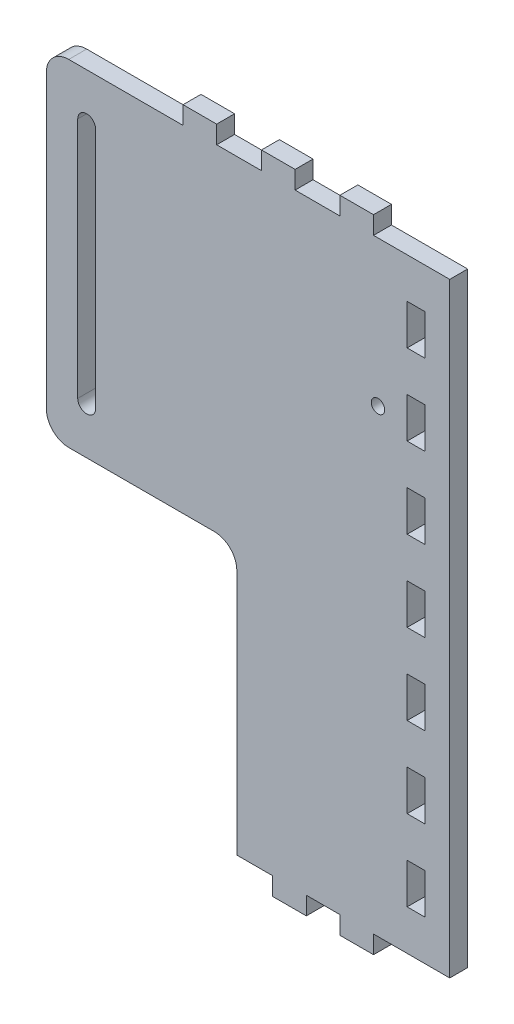
SolidWorks part; units mm, degrees
material "Beech"
ref_plane "Front" through (0, 0, 0) normal (0, 0, 1) x (1, 0, 0)
ref_plane "Top" through (0, 0, 0) normal (0, 1, 0) x (1, 0, 0)
ref_plane "Right" through (0, 0, 0) normal (1, 0, 0) x (0, 0, -1)
sketch "Sketch1" plane through (0, 0, 0) normal (0, 0, 1) x (1, 0, 0)
  line L0 (58, 135) -> (58, 70) construction
  line L1 (-90, -135) -> (90, -135) construction
  line L2 (-90, -135) -> (-90, 135) construction
  line L3 (-90, 135) -> (90, 135) construction
  line L4 (90, -135) -> (90, 135) construction
  line L5 (-90, -135) -> (90, 135) construction
  line L6 (-90, 135) -> (90, -135) construction
  line L7 (58, 70) -> (90, 70) construction
  line L8 (-90, -15) -> (90, -15) construction
  line L9 (-76, 135) -> (-76, -15) construction
  line L10 (-68, -15) -> (-68, 135) construction
  line L11 (-5, -15) -> (-5, -135) construction
  line L12 (90, 135) -> (-80, 135)
  line L13 (-90, 125) -> (-90, -5)
  line L14 (-80, -15) -> (-15, -15)
  line L15 (-5, -25) -> (-5, -135)
  line L16 (-5, -135) -> (90, -135)
  line L17 (90, -135) -> (90, 135)
  line L18 (-72, 114) -> (-72, 6) construction
  line L19 (-68, 114) -> (-68, 6)
  line L20 (-76, 114) -> (-76, 6)
  arc A0 (-68, 114) -> (-76, 114) centre (-72, 114) ccw
  arc A1 (-76, 6) -> (-68, 6) centre (-72, 6) ccw
  circle A2 centre (58, 70) radius 3
  arc A3 (-15, -15) -> (-5, -25) centre (-15, -25) cw
  arc A4 (-90, -5) -> (-80, -15) centre (-80, -5) ccw
  arc A5 (-80, 135) -> (-90, 125) centre (-80, 125) ccw
  point P0 (0, 0)
  point P19 (-72, 60)
  point P25 (-68, 60)
  point P26 (-76, 60)
  point P36 (0, 0)
  point P37 (0, 0)
  dimension "D10" = 6
  dimension "D11" = 10
  dimension "D1" = 180
  dimension "D2" = 120
  dimension "D3" = 270
  dimension "D4" = 95
  dimension "D5" = 14
  dimension "D6" = 8
  dimension "D7" = 65
  dimension "D8" = 32
  dimension "D9" = 108
extrude "Boss-Extrude1" add sketch "Sketch1" along normal blind 8
sketch "Sketch2" plane through (0, 0, 8) normal (0, 0, 1) x (1, 0, 0)
  line L0 (90, -135) -> (90, 135) construction
  line L1 (79, -117) -> (71, -117)
  line L2 (79, -117) -> (79, -99)
  line L3 (79, -99) -> (71, -99)
  line L4 (71, -117) -> (71, -99)
  line L5 (79, -117) -> (71, -99) construction
  line L6 (79, -99) -> (71, -117) construction
  line L7 (-5, -135) -> (90, -135) construction
  line L8 (79, -63) -> (71, -63)
  line L9 (71, -81) -> (71, -63)
  line L10 (79, -81) -> (71, -81)
  line L11 (79, -81) -> (79, -63)
  line L12 (79, -27) -> (71, -27)
  line L13 (71, -45) -> (71, -27)
  line L14 (79, -45) -> (71, -45)
  line L15 (79, -45) -> (79, -27)
  line L16 (79, 9) -> (71, 9)
  line L17 (71, -9) -> (71, 9)
  line L18 (79, -9) -> (71, -9)
  line L19 (79, -9) -> (79, 9)
  line L20 (79, 45) -> (71, 45)
  line L21 (71, 27) -> (71, 45)
  line L22 (79, 27) -> (71, 27)
  line L23 (79, 27) -> (79, 45)
  line L24 (79, 81) -> (71, 81)
  line L25 (71, 63) -> (71, 81)
  line L26 (79, 63) -> (71, 63)
  line L27 (79, 63) -> (79, 81)
  line L28 (79, 117) -> (71, 117)
  line L29 (71, 99) -> (71, 117)
  line L30 (79, 99) -> (71, 99)
  line L31 (79, 99) -> (79, 117)
  point P4 (75, -108)
  dimension "D1" = 11
  dimension "D2" = 18
  dimension "D3" = 18
  dimension "D4" = 8
  dimension "D6" = 18
  dimension "D5" = 7
extrude "Cut-Extrude1" cut sketch "Sketch2" against normal through all
sketch "Sketch3" plane through (0, -135, 0) normal (0, -1, 0) x (1, 0, 0)
  line L2 (-5, 0) -> (90, 0) construction
  line L3 (56, 0) -> (41, 0)
  line L4 (56, 0) -> (56, 8)
  line L5 (56, 8) -> (41, 8)
  line L6 (41, 0) -> (41, 8)
  line L7 (56, 0) -> (41, 8) construction
  line L8 (56, 8) -> (41, 0) construction
  line L9 (-5, 8) -> (90, 8) construction
  line L10 (90, 8) -> (90, 0) construction
  line L11 (26, 0) -> (11, 0)
  line L12 (11, 0) -> (11, 8)
  line L13 (26, 8) -> (11, 8)
  line L14 (26, 0) -> (26, 8)
  line L19 (-4, 0) -> (-19, 0) [skipped]
  line L20 (-19, 0) -> (-19, 8) [skipped]
  line L21 (-4, 8) -> (-19, 8) [skipped]
  line L22 (-4, 0) -> (-4, 8) [skipped]
  point P4 (48.5, 4)
  dimension "D1" = 34
  dimension "D2" = 15
  dimension "D4" = 15
  dimension "D3" = 3
extrude "Boss-Extrude2" add sketch "Sketch3" along normal blind 8
sketch "Sketch4" plane through (0, 135, 0) normal (0, 1, 0) x (1, 0, 0)
  line L0 (90, -8) -> (-80, -8) construction
  line L1 (56, -8) -> (41, -8)
  line L2 (56, -8) -> (56, 0)
  line L3 (56, 0) -> (41, 0)
  line L4 (41, -8) -> (41, 0)
  line L5 (56, -8) -> (41, 0) construction
  line L6 (56, 0) -> (41, -8) construction
  line L7 (90, 0) -> (-80, 0) construction
  line L8 (90, -8) -> (90, 0) construction
  line L9 (21, 0) -> (6, 0)
  line L10 (6, -8) -> (6, 0)
  line L11 (21, -8) -> (6, -8)
  line L12 (21, -8) -> (21, 0)
  line L13 (-14, 0) -> (-29, 0)
  line L14 (-29, -8) -> (-29, 0)
  line L15 (-14, -8) -> (-29, -8)
  line L16 (-14, -8) -> (-14, 0)
  point P4 (48.5, -4)
  dimension "D1" = 34
  dimension "D2" = 15
  dimension "D3" = 3
extrude "Boss-Extrude3" add sketch "Sketch4" along normal blind 8
